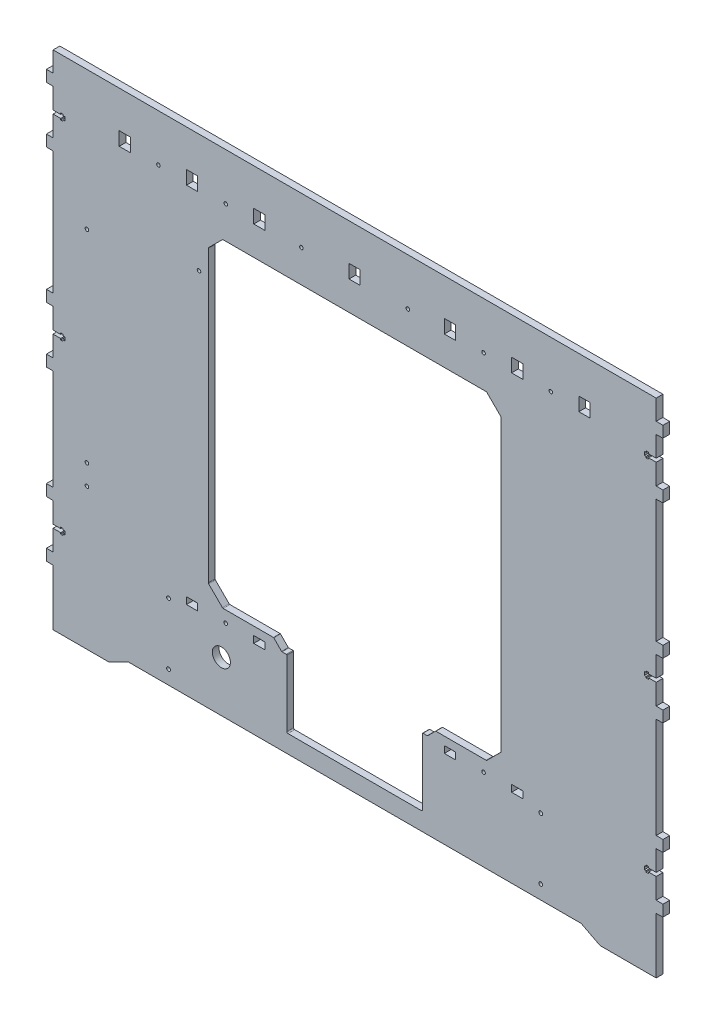
SolidWorks part; units mm, degrees
material "Клен"
ref_plane "Front" through (0, 0, 0) normal (0, 0, 1) x (1, 0, 0)
ref_plane "Top" through (0, 0, 0) normal (0, 1, 0) x (1, 0, 0)
ref_plane "Right" through (0, 0, 0) normal (1, 0, 0) x (0, 0, -1)
sketch "Эскиз2" plane through (0, 0, 0) normal (0, 0, 1) x (1, 0, 0)
  line L0 (400.4244, 482.0072) -> (-19.6784, 482.0072) construction
  line L1 (308.1919, 504.8221) -> (308.1919, 0) construction
  line L2 (39.1919, 504.8221) -> (39.1919, 18.7975) construction
  line L3 (33.1919, 504.8221) -> (33.1919, 18.7975) construction
  line L4 (228.1919, 149.8356) -> (228.1919, 102.1072) construction
  line L5 (168.1919, 135.3857) -> (168.1919, 108.8729) construction
  line L6 (193.1919, 141.9072) -> (193.1919, 108.8729) construction
  line L7 (260.6919, 457.1072) -> (260.6919, 439.2572) construction
  line L8 (228.1919, 461.9072) -> (228.1919, 439.2572) construction
  line L13 (193.1919, 457.1072) -> (193.1919, 440.4572) construction
  line L18 (39.1919, 477.0072) -> (39.1919, 472.1072)
  line L19 (39.1919, 472.1072) -> (33.1919, 472.0072)
  line L20 (33.1919, 472.0072) -> (33.1919, 462.0072)
  line L21 (33.1919, 462.0072) -> (39.1919, 461.9072)
  line L22 (39.1919, 461.9072) -> (39.1919, 443.5572)
  line L23 (39.1919, 443.5572) -> (45.9919, 443.5572)
  line L24 (45.9919, 443.5572) -> (45.9919, 444.7572)
  line L25 (45.9919, 444.7572) -> (48.1919, 444.7572)
  line L26 (48.1919, 444.7572) -> (48.1919, 443.5572)
  line L27 (48.1919, 443.5572) -> (49.6919, 443.5572)
  line L28 (49.6919, 443.5572) -> (49.6919, 440.4572)
  line L29 (49.6919, 440.4572) -> (48.1919, 440.4572)
  line L30 (48.1919, 440.4572) -> (48.1919, 439.2572)
  line L31 (48.1919, 439.2572) -> (45.9919, 439.2572)
  line L32 (45.9919, 439.2572) -> (45.9919, 440.4572)
  line L33 (45.9919, 440.4572) -> (39.1919, 440.4572)
  line L34 (39.1919, 440.4572) -> (39.1919, 422.1072)
  line L35 (39.1919, 422.1072) -> (33.1919, 422.0072)
  line L36 (33.1919, 422.0072) -> (33.1919, 412.0072)
  line L37 (33.1919, 412.0072) -> (39.1919, 411.9072)
  line L38 (39.1919, 411.9072) -> (39.1919, 302.1072)
  line L39 (39.1919, 302.1072) -> (33.1919, 302.0072)
  line L40 (33.1919, 302.0072) -> (33.1919, 292.0072)
  line L41 (33.1919, 292.0072) -> (39.1919, 291.9072)
  line L42 (39.1919, 291.9072) -> (39.1919, 273.5572)
  line L43 (39.1919, 273.5572) -> (45.9919, 273.5572)
  line L44 (45.9919, 273.5572) -> (45.9919, 274.7572)
  line L45 (45.9919, 274.7572) -> (48.1919, 274.7572)
  line L46 (48.1919, 274.7572) -> (48.1919, 273.5572)
  line L47 (48.1919, 273.5572) -> (49.6919, 273.5572)
  line L48 (49.6919, 273.5572) -> (49.6919, 270.4572)
  line L49 (49.6919, 270.4572) -> (48.1919, 270.4572)
  line L50 (48.1919, 270.4572) -> (48.1919, 269.2572)
  line L51 (48.1919, 269.2572) -> (45.9919, 269.2572)
  line L52 (45.9919, 269.2572) -> (45.9919, 270.4572)
  line L53 (45.9919, 270.4572) -> (39.1919, 270.4572)
  line L54 (39.1919, 270.4572) -> (39.1919, 252.1072)
  line L55 (39.1919, 252.1072) -> (33.1919, 252.0072)
  line L56 (33.1919, 252.0072) -> (33.1919, 242.0072)
  line L57 (33.1919, 242.0072) -> (39.1919, 241.9072)
  line L58 (39.1919, 241.9072) -> (39.1919, 152.1072)
  line L59 (39.1919, 152.1072) -> (33.1919, 152.0072)
  line L60 (33.1919, 152.0072) -> (33.1919, 142.0072)
  line L61 (33.1919, 142.0072) -> (39.1919, 141.9072)
  line L62 (39.1919, 141.9072) -> (39.1919, 123.5572)
  line L63 (39.1919, 123.5572) -> (45.9919, 123.5572)
  line L64 (45.9919, 123.5572) -> (45.9919, 124.7572)
  line L65 (45.9919, 124.7572) -> (48.1919, 124.7572)
  line L66 (48.1919, 124.7572) -> (48.1919, 123.5572)
  line L67 (48.1919, 123.5572) -> (49.6919, 123.5572)
  line L68 (49.6919, 123.5572) -> (49.6919, 120.4572)
  line L69 (49.6919, 120.4572) -> (48.1919, 120.4572)
  line L70 (48.1919, 120.4572) -> (48.1919, 119.2572)
  line L71 (48.1919, 119.2572) -> (45.9919, 119.2572)
  line L72 (45.9919, 119.2572) -> (45.9919, 120.4572)
  line L73 (45.9919, 120.4572) -> (39.1919, 120.4572)
  line L74 (39.1919, 120.4572) -> (39.1919, 102.1072)
  line L75 (39.1919, 102.1072) -> (33.1919, 102.0072)
  line L76 (33.1919, 102.0072) -> (33.1919, 92.0072)
  line L77 (33.1919, 92.0072) -> (39.1919, 91.9072)
  line L78 (39.1919, 91.9072) -> (39.1919, 42.0072)
  line L79 (39.1919, 42.0072) -> (89.1919, 42.0072)
  line L80 (89.1919, 42.0072) -> (106.1919, 50.7072)
  line L81 (106.1919, 50.7072) -> (510.1919, 50.7072)
  line L82 (313.1919, 457.1072) -> (303.1919, 457.1072)
  line L83 (168.1919, 461.9072) -> (168.1919, 439.2572) construction
  line L84 (303.1919, 457.1072) -> (303.1919, 445.0072)
  line L85 (303.1919, 445.0072) -> (313.1919, 445.0072)
  line L86 (267.1919, 490.0072) -> (577.1919, 490.0072)
  line L87 (169.3644, 152.1072) -> (169.3644, 392.271) construction
  line L88 (218.1919, 127.1049) -> (228.1919, 127.1049)
  line L89 (218.1919, 127.1049) -> (218.1919, 121.0049)
  line L90 (218.1919, 121.0049) -> (228.1919, 121.0049)
  line L91 (228.1919, 127.1049) -> (228.1919, 121.0049)
  line L92 (158.1919, 127.1049) -> (168.1919, 127.1049)
  line L93 (158.1919, 127.1049) -> (158.1919, 121.0049)
  line L94 (158.1919, 121.0049) -> (168.1919, 121.0049)
  line L95 (168.1919, 127.1049) -> (168.1919, 121.0049)
  line L96 (158.1919, 457.1072) -> (168.1919, 457.1072)
  line L97 (158.1919, 457.1072) -> (158.1919, 445.0072)
  line L98 (158.1919, 445.0072) -> (168.1919, 445.0072)
  line L99 (168.1919, 457.1072) -> (168.1919, 445.0072)
  line L100 (218.1919, 457.1072) -> (228.1919, 457.1072)
  line L101 (218.1919, 457.1072) -> (218.1919, 445.0072)
  line L102 (218.1919, 445.0072) -> (228.1919, 445.0072)
  line L103 (228.1919, 457.1072) -> (228.1919, 445.0072)
  line L104 (577.1919, 490.0072) -> (577.1919, 477.0072)
  line L105 (367.6919, 66.6049) -> (248.6919, 66.6049)
  line L106 (267.1919, 490.0072) -> (39.1919, 490.0072)
  line L107 (247.6919, 67.6049) -> (247.6919, 126.6049)
  line L108 (247.1919, 127.1049) -> (243.399, 127.1049)
  line L109 (239.5515, 130.7453) -> (243.0455, 127.2514)
  line L110 (39.1919, 490.0072) -> (39.1919, 477.0072)
  line L111 (239.5515, 130.7453) -> (236.0575, 134.2393)
  line L112 (213.3308, 134.3857) -> (235.704, 134.3857)
  line L113 (108.1919, 457.1072) -> (108.1919, 445.0072)
  line L114 (213.3308, 134.3857) -> (190.9576, 134.3857)
  line L115 (184.1064, 140.7795) -> (190.253, 134.6761)
  line L116 (98.1919, 445.0072) -> (108.1919, 445.0072)
  line L117 (184.1064, 140.7795) -> (177.9598, 146.8828)
  line L118 (177.6644, 169.7011) -> (177.6644, 147.5924)
  line L119 (98.1919, 457.1072) -> (108.1919, 457.1072)
  line L120 (177.6644, 169.7011) -> (177.6644, 405.9627)
  line L121 (184.1064, 412.7756) -> (177.9598, 406.6723)
  line L122 (98.1919, 457.1072) -> (98.1919, 445.0072)
  line L123 (184.1064, 412.7756) -> (190.253, 418.8789)
  line L124 (308.1379, 419.1693) -> (190.9576, 419.1693)
  line L125 (518.1919, 457.1072) -> (508.1919, 457.1072)
  line L126 (308.2459, 419.1693) -> (425.4263, 419.1693)
  line L127 (432.2775, 412.7756) -> (426.1309, 418.8789)
  line L128 (432.2775, 412.7756) -> (438.4241, 406.6723)
  line L129 (438.7195, 169.7011) -> (438.7195, 405.9627)
  line L130 (438.7195, 169.7011) -> (438.7195, 147.5924)
  line L131 (432.2775, 140.7795) -> (438.4241, 146.8828)
  line L132 (432.2775, 140.7795) -> (426.1309, 134.6761)
  line L133 (403.0531, 134.3857) -> (425.4263, 134.3857)
  line L134 (403.0531, 134.3857) -> (380.6799, 134.3857)
  line L135 (376.8323, 130.7453) -> (380.3263, 134.2393)
  line L136 (376.8323, 130.7453) -> (373.3384, 127.2514)
  line L137 (369.1919, 127.1049) -> (372.9848, 127.1049)
  line L138 (368.6919, 67.6049) -> (368.6919, 126.6049)
  line L139 (388.1919, 457.1072) -> (388.1919, 445.0072)
  line L140 (398.1919, 445.0072) -> (388.1919, 445.0072)
  line L141 (398.1919, 457.1072) -> (398.1919, 445.0072)
  line L142 (398.1919, 457.1072) -> (388.1919, 457.1072)
  line L143 (448.1919, 457.1072) -> (448.1919, 445.0072)
  line L144 (458.1919, 445.0072) -> (448.1919, 445.0072)
  line L145 (458.1919, 457.1072) -> (458.1919, 445.0072)
  line L146 (458.1919, 457.1072) -> (448.1919, 457.1072)
  line L147 (448.1919, 127.1049) -> (448.1919, 121.0049)
  line L148 (458.1919, 121.0049) -> (448.1919, 121.0049)
  line L149 (458.1919, 127.1049) -> (458.1919, 121.0049)
  line L150 (458.1919, 127.1049) -> (448.1919, 127.1049)
  line L151 (388.1919, 127.1049) -> (388.1919, 121.0049)
  line L152 (398.1919, 121.0049) -> (388.1919, 121.0049)
  line L153 (398.1919, 127.1049) -> (398.1919, 121.0049)
  line L154 (398.1919, 127.1049) -> (388.1919, 127.1049)
  line L155 (313.1919, 457.1072) -> (313.1919, 445.0072)
  line L156 (527.1919, 42.0072) -> (510.1919, 50.7072)
  line L157 (577.1919, 42.0072) -> (527.1919, 42.0072)
  line L158 (577.1919, 91.9072) -> (577.1919, 42.0072)
  line L159 (583.1919, 92.0072) -> (577.1919, 91.9072)
  line L160 (583.1919, 102.0072) -> (583.1919, 92.0072)
  line L161 (577.1919, 102.1072) -> (583.1919, 102.0072)
  line L162 (577.1919, 120.4572) -> (577.1919, 102.1072)
  line L163 (570.3919, 120.4572) -> (577.1919, 120.4572)
  line L164 (570.3919, 119.2572) -> (570.3919, 120.4572)
  line L165 (568.1919, 119.2572) -> (570.3919, 119.2572)
  line L166 (568.1919, 120.4572) -> (568.1919, 119.2572)
  line L167 (566.6919, 120.4572) -> (568.1919, 120.4572)
  line L168 (566.6919, 123.5572) -> (566.6919, 120.4572)
  line L169 (568.1919, 123.5572) -> (566.6919, 123.5572)
  line L170 (568.1919, 124.7572) -> (568.1919, 123.5572)
  line L171 (570.3919, 124.7572) -> (568.1919, 124.7572)
  line L172 (570.3919, 123.5572) -> (570.3919, 124.7572)
  line L173 (577.1919, 123.5572) -> (570.3919, 123.5572)
  line L174 (577.1919, 141.9072) -> (577.1919, 123.5572)
  line L175 (583.1919, 142.0072) -> (577.1919, 141.9072)
  line L176 (583.1919, 152.0072) -> (583.1919, 142.0072)
  line L177 (577.1919, 152.1072) -> (583.1919, 152.0072)
  line L178 (577.1919, 241.9072) -> (577.1919, 152.1072)
  line L179 (583.1919, 242.0072) -> (577.1919, 241.9072)
  line L180 (583.1919, 252.0072) -> (583.1919, 242.0072)
  line L181 (577.1919, 252.1072) -> (583.1919, 252.0072)
  line L182 (577.1919, 270.4572) -> (577.1919, 252.1072)
  line L183 (570.3919, 270.4572) -> (577.1919, 270.4572)
  line L184 (570.3919, 269.2572) -> (570.3919, 270.4572)
  line L185 (568.1919, 269.2572) -> (570.3919, 269.2572)
  line L186 (568.1919, 270.4572) -> (568.1919, 269.2572)
  line L187 (566.6919, 270.4572) -> (568.1919, 270.4572)
  line L188 (566.6919, 273.5572) -> (566.6919, 270.4572)
  line L189 (568.1919, 273.5572) -> (566.6919, 273.5572)
  line L190 (568.1919, 274.7572) -> (568.1919, 273.5572)
  line L191 (570.3919, 274.7572) -> (568.1919, 274.7572)
  line L192 (570.3919, 273.5572) -> (570.3919, 274.7572)
  line L193 (577.1919, 273.5572) -> (570.3919, 273.5572)
  line L194 (577.1919, 291.9072) -> (577.1919, 273.5572)
  line L195 (583.1919, 292.0072) -> (577.1919, 291.9072)
  line L196 (583.1919, 302.0072) -> (583.1919, 292.0072)
  line L197 (577.1919, 302.1072) -> (583.1919, 302.0072)
  line L198 (577.1919, 411.9072) -> (577.1919, 302.1072)
  line L199 (583.1919, 412.0072) -> (577.1919, 411.9072)
  line L200 (583.1919, 422.0072) -> (583.1919, 412.0072)
  line L201 (577.1919, 422.1072) -> (583.1919, 422.0072)
  line L202 (577.1919, 440.4572) -> (577.1919, 422.1072)
  line L203 (570.3919, 440.4572) -> (577.1919, 440.4572)
  line L204 (570.3919, 439.2572) -> (570.3919, 440.4572)
  line L205 (568.1919, 439.2572) -> (570.3919, 439.2572)
  line L206 (568.1919, 440.4572) -> (568.1919, 439.2572)
  line L207 (566.6919, 440.4572) -> (568.1919, 440.4572)
  line L208 (566.6919, 443.5572) -> (566.6919, 440.4572)
  line L209 (568.1919, 443.5572) -> (566.6919, 443.5572)
  line L210 (568.1919, 444.7572) -> (568.1919, 443.5572)
  line L211 (570.3919, 444.7572) -> (568.1919, 444.7572)
  line L212 (570.3919, 443.5572) -> (570.3919, 444.7572)
  line L213 (577.1919, 443.5572) -> (570.3919, 443.5572)
  line L214 (577.1919, 461.9072) -> (577.1919, 443.5572)
  line L215 (583.1919, 462.0072) -> (577.1919, 461.9072)
  line L216 (583.1919, 472.0072) -> (583.1919, 462.0072)
  line L217 (577.1919, 472.1072) -> (583.1919, 472.0072)
  line L218 (577.1919, 477.0072) -> (577.1919, 472.1072)
  line L226 (308.1379, 419.1693) -> (308.2459, 419.1693)
  line L227 (508.1919, 457.1072) -> (508.1919, 445.0072)
  line L228 (518.1919, 457.1072) -> (518.1919, 445.0072)
  line L229 (518.1919, 445.0072) -> (508.1919, 445.0072)
  circle A4 centre (260.6919, 448.0572) radius 1.6
  circle A5 centre (193.1919, 448.0572) radius 1.6
  circle A6 centre (169.3644, 384.4593) radius 1.6
  circle A7 centre (69.3644, 366.4593) radius 1.6
  circle A8 centre (69.3644, 186.0893) radius 1.6
  circle A9 centre (69.3644, 168.0893) radius 1.6
  circle A10 centre (193.1919, 124.0549) radius 1.6
  circle A11 centre (142.1919, 117.9049) radius 1.7
  circle A12 centre (142.1919, 63.1049) radius 1.7
  circle A13 centre (189.3045, 95.8269) radius 8.05
  arc A14 (248.6919, 66.6049) -> (247.6919, 67.6049) centre (248.6919, 67.6049) cw
  arc A15 (247.6919, 126.6049) -> (247.1919, 127.1049) centre (247.1919, 126.6049) ccw
  arc A16 (243.0455, 127.2514) -> (243.399, 127.1049) centre (243.399, 127.6049) ccw
  arc A17 (236.0575, 134.2393) -> (235.704, 134.3857) centre (235.704, 133.8857) ccw
  arc A18 (190.9576, 419.1693) -> (190.253, 418.8789) centre (190.9576, 418.1693) ccw
  arc A19 (177.9598, 406.6723) -> (177.6644, 405.9627) centre (178.6644, 405.9627) ccw
  arc A20 (177.9598, 146.8828) -> (177.6644, 147.5924) centre (178.6644, 147.5924) cw
  arc A21 (190.9576, 134.3857) -> (190.253, 134.6761) centre (190.9576, 135.3857) cw
  arc A22 (425.4263, 134.3857) -> (426.1309, 134.6761) centre (425.4263, 135.3857) ccw
  arc A23 (438.4241, 146.8828) -> (438.7195, 147.5924) centre (437.7195, 147.5924) ccw
  arc A24 (438.4241, 406.6723) -> (438.7195, 405.9627) centre (437.7195, 405.9627) cw
  arc A25 (425.4263, 419.1693) -> (426.1309, 418.8789) centre (425.4263, 418.1693) cw
  arc A26 (380.3263, 134.2393) -> (380.6799, 134.3857) centre (380.6799, 133.8857) cw
  arc A27 (373.3384, 127.2514) -> (372.9848, 127.1049) centre (372.9848, 127.6049) cw
  arc A28 (368.6919, 126.6049) -> (369.1919, 127.1049) centre (369.1919, 126.6049) cw
  arc A29 (367.6919, 66.6049) -> (368.6919, 67.6049) centre (367.6919, 67.6049) ccw
  circle A30 centre (474.1919, 63.1049) radius 1.7
  circle A31 centre (474.1919, 117.9049) radius 1.7
  circle A32 centre (423.1919, 124.0549) radius 1.6
  circle A33 centre (423.1919, 448.0572) radius 1.6
  circle A34 centre (355.6919, 448.0572) radius 1.6
  circle A35 centre (483.1919, 448.0572) radius 1.6
  circle A36 centre (133.1919, 448.0572) radius 1.6
  point P331 (308.1919, 66.6049)
  point P348 (308.1919, 445.0072)
  point P349 (308.1919, 457.1072)
  dimension "D5" = 1
  dimension "D6" = 0.5
  dimension "D7" = 0.5
  dimension "D8" = 0.5
  dimension "D9" = 1
  dimension "D10" = 1
  dimension "D11" = 1
  dimension "D12" = 1
  dimension "D15" = 58.3874
  dimension "D13" = 6
  dimension "D14" = 269
  dimension "D16" = 47.5
  dimension "D17" = 32.5
  dimension "D18" = 35
  dimension "D19" = 25
  dimension "D21" = 138.8276
  dimension "D22" = 80
  dimension "D23" = 35
  dimension "D24" = 25
extrude "Бобышка-Вытянуть2" add sketch "Эскиз2" along normal blind 6
